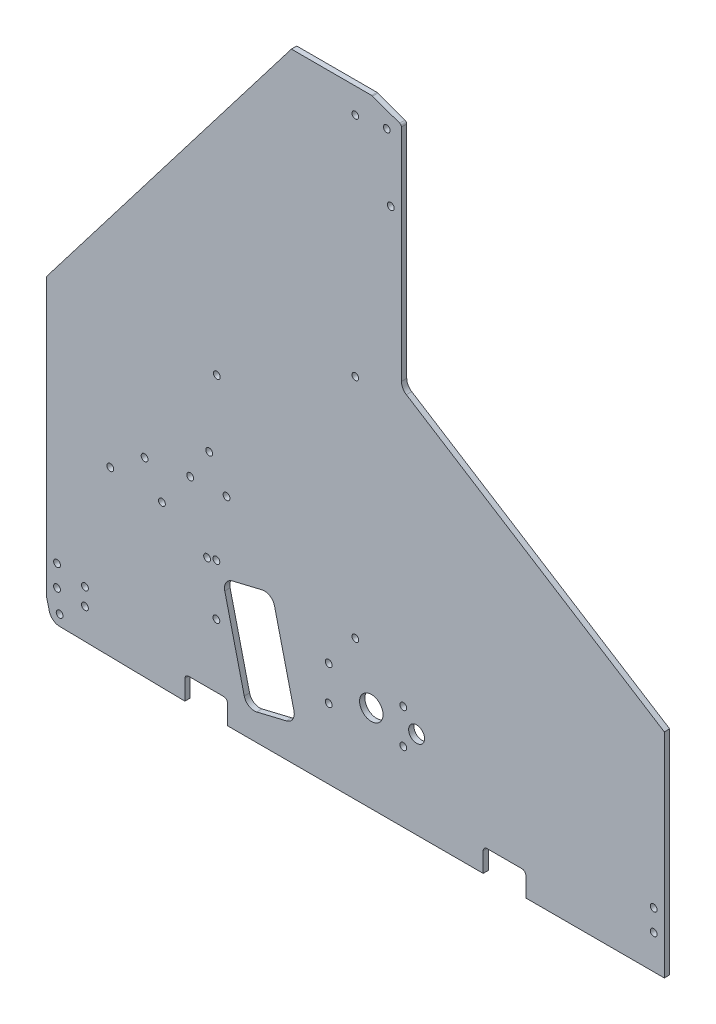
SolidWorks part; units mm, degrees
ref_plane "Front Plane" through (0, 0, 0) normal (0, 0, 1) x (1, 0, 0)
ref_plane "Top Plane" through (0, 0, 0) normal (0, 1, 0) x (1, 0, 0)
ref_plane "Right Plane" through (0, 0, 0) normal (1, 0, 0) x (0, 0, -1)
sketch "Sketch1" plane through (0, 0, 0) normal (0, 0, 1) x (1, 0, 0)
  line L0 (82.55, -20.32) -> (82.55, -6.35)
  line L2 (0, 0) -> (0, 157.48)
  line L4 (368.3, -20.32) -> (368.3, 106.68)
  line L5 (82.55, -6.35) -> (107.95, -6.35)
  line L6 (107.95, -6.35) -> (107.95, -20.32)
  line L7 (107.95, -20.32) -> (260.35, -20.32)
  line L8 (260.35, -20.32) -> (260.35, -6.35)
  line L9 (260.35, -6.35) -> (285.75, -6.35)
  line L10 (285.75, -6.35) -> (285.75, -20.32)
  line L11 (285.75, -20.32) -> (368.3, -20.32)
  line L12 (361.95, 12.7) -> (368.3, 12.7) construction
  line L13 (0, 0) -> (6.35, 0) construction
  line L14 (0.1896, -7.8901) -> (1.7771, -14.2401)
  line L15 (7.8295, -19.0491) -> (82.55, -20.32)
  line L16 (0, 0) -> (0, -6.35)
  line L17 (85.725, 97.155) -> (82.9754, 95.5675) construction
  line L18 (97.0634, 115.6163) -> (58.5686, 93.3913) construction
  line L19 (97.0634, 115.6163) -> (107.3822, 97.7437) construction
  line L20 (58.5686, 93.3913) -> (68.8873, 75.5187) construction
  line L21 (107.3822, 97.7437) -> (68.8873, 75.5187) construction
  line L22 (97.0634, 115.6163) -> (68.8873, 75.5187) construction
  line L23 (58.5686, 93.3913) -> (107.3822, 97.7437) construction
  line L24 (7.9375, -12.7) -> (95.7973, 60.4105) construction
  line L25 (184.15, 62.98) -> (184.15, 197.98) construction
  line L26 (184.15, 197.98) -> (184.15, 332.98) construction
  line L27 (355.6, 335.28) -> (330.2, 335.28) construction
  line L28 (330.2, 335.28) -> (330.2, 220.98) construction
  line L29 (330.2, 220.98) -> (355.6, 220.98) construction
  line L30 (355.6, 220.98) -> (355.6, 335.28) construction
  line L31 (184.15, 347.98) -> (184.15, 269.4703) construction
  line L32 (12.7, 335.28) -> (38.1, 335.28) construction
  line L33 (38.1, 335.28) -> (38.1, 220.98) construction
  line L34 (12.7, 220.98) -> (12.7, 335.28) construction
  line L35 (38.1, 220.98) -> (12.7, 220.98) construction
  line L36 (194.15, 347.98) -> (211.6138, 341.63)
  line L37 (184.15, 347.98) -> (146.05, 347.98)
  line L38 (184.15, 347.98) -> (194.15, 347.98)
  line L39 (348.5362, 347.98) -> (413.4623, 347.98)
  line L40 (348.5362, 347.98) -> (211.6138, 347.98) construction
  line L42 (146.05, 347.98) -> (0, 157.48)
  line L44 (211.6138, 341.63) -> (211.6138, 205.74)
  line L45 (211.6138, 205.74) -> (368.3, 106.68)
  line L46 (194.15, 347.98) -> (-141.0713, 347.98) construction
  circle A0 centre (6.35, 0) radius 2.032
  circle A1 centre (6.35, 12.7) radius 2.032
  circle A2 centre (361.95, 0) radius 2.032
  circle A3 centre (361.95, 12.7) radius 2.032
  arc A5 (1.7771, -14.2401) -> (7.8295, -19.0491) centre (7.9375, -12.7) ccw
  circle A6 centre (7.9375, -12.7) radius 2.032
  arc A7 (0, -6.35) -> (0.1896, -7.8901) centre (6.35, -6.35) ccw
  circle A8 centre (38.1, 78.105) radius 2.032
  circle A9 centre (85.725, 97.155) radius 2.032
  circle A10 centre (58.5686, 93.3913) radius 2.032
  circle A11 centre (68.8873, 75.5187) radius 2.032
  circle A12 centre (107.3822, 97.7437) radius 2.032
  circle A13 centre (97.0634, 115.6163) radius 2.032
  circle A14 centre (95.7973, 60.4105) radius 2.032
  circle A15 centre (184.15, 62.98) radius 2
  circle A16 centre (184.15, 197.98) radius 2
  circle A17 centre (184.15, 332.98) radius 2
  circle A18 centre (63.5, 316.23) radius 2.032
  circle A19 centre (101.6, 157.48) radius 2.032
  circle A20 centre (355.6, 335.28) radius 2.032
  circle A21 centre (330.2, 335.28) radius 2.032
  circle A22 centre (355.6, 220.98) radius 2.032
  circle A23 centre (330.2, 220.98) radius 2.032
  circle A24 centre (12.7, 335.28) radius 2.032
  circle A25 centre (38.1, 335.28) radius 2.032
  circle A26 centre (12.7, 220.98) radius 2.032
  circle A27 centre (38.1, 220.98) radius 2.032
  circle A28 centre (202.8819, 335.28) radius 2
  circle A29 centre (205.2638, 296.418) radius 2.032
  point P82 (184.15, 347.98)
  point P83 (202.8819, 344.805)
  dimension "D6" = 4.064
  dimension "D10" = 6.35
  dimension "D11" = 4.064
  dimension "D17" = 38.1
  dimension "D27" = 4
  dimension "D31" = 4.064
  dimension "D32" = 38.1
  dimension "D36" = 4.064
  dimension "D47" = 45.212
  dimension "D48" = 4.064
  dimension "D2" = 127
  dimension "D3" = 13.97
  dimension "D4" = 25.4
  dimension "D5" = 152.4
  dimension "D7" = 12.7
  dimension "D8" = 6.35
  dimension "D9" = 20.32
  dimension "D12" = 12.7
  dimension "D13" = 1.5875
  dimension "D14" = 82.55
  dimension "D15" = 368.3
  dimension "D16" = 6.35
  dimension "D18" = 98.425
  dimension "D19" = 47.625
  dimension "D20" = 19.05
  dimension "D21" = 3.175
  dimension "D22" = 60
  dimension "D23" = 20.6375
  dimension "D24" = 44.45
  dimension "D25" = 38.1
  dimension "D26" = 114.3
  dimension "D28" = 135
  dimension "D29" = 12.7
  dimension "D30" = 15
  dimension "D33" = 63.5
  dimension "D34" = 27.4638
  dimension "D35" = 101.6
  dimension "D37" = 114.3
  dimension "D38" = 25.4
  dimension "D39" = 12.7
  dimension "D40" = 157.48
  dimension "D41" = 142.24
  dimension "D42" = 368.3
  dimension "D43" = 10
  dimension "D44" = 6.35
  dimension "D45" = 31.75
  dimension "D46" = 6.35
  dimension "D49" = 6.35
extrude "Boss-Extrude1" add sketch "Sketch1" along normal blind 3.175 contours L16 A7 L14 A5 L15 L2 A0 A1 A6 region at (167.8922, 118.3155, 0)
fillet "Fillet1" radius 2.286 4 edges at (285.75, -6.35, 1.5875) (107.95, -6.35, 1.5875) (260.35, -6.35, 1.5875) (82.55, -6.35, 1.5875)
fillet "Fillet2" radius 6.35 1 edges at (211.6138, 205.74, 1.5875)
sketch "Sketch2" plane through (0, 0, 0) normal (0, 0, -1) x (-1, 0, 0)
  circle A0 centre (-101.3398, 61.8475) radius 2.032 construction
  circle A1 centre (-101.3398, 31.3675) radius 2.032 construction
  circle A2 centre (-23.012, 8.964) radius 2.032 construction
  circle A3 centre (-23.012, -1.196) radius 2.032 construction
  circle A4 centre (-101.3398, 61.8475) radius 2.032
  circle A5 centre (-101.3398, 31.3675) radius 2.032
  circle A6 centre (-23.012, 8.964) radius 2.032
  circle A7 centre (-23.012, -1.196) radius 2.032
extrude "Cut-Extrude1" cut sketch "Sketch2" against normal through all
fillet "Fillet3" radius 1.5875 2 edges at (211.6138, 341.63, 1.5875) (194.15, 347.98, 1.5875)
sketch "Sketch3" plane through (0, 0, 3.175) normal (0, 0, 1) x (1, 0, 0)
  line L0 (133.7394, 54.026) -> (133.5085, 54.9896) construction
  line L1 (129.1684, 57.6512) -> (111.4698, 53.4086) construction
  line L2 (115.3002, 49.1851) -> (127.6692, 52.1501) construction
  line L3 (108.8082, 49.0686) -> (109.0392, 48.1051) construction
  line L4 (131.9876, 48.4644) -> (140.8034, 11.688) construction
  line L5 (144.8863, 7.5251) -> (133.7394, 54.026) construction
  line L6 (109.0392, 48.1051) -> (120.1861, 1.6041) construction
  line L7 (121.9379, 7.1657) -> (113.1221, 43.9421) construction
  line L8 (120.1861, 1.6041) -> (120.4171, 0.6406) construction
  line L9 (145.1173, 6.5615) -> (144.8863, 7.5251) construction
  line L10 (138.6253, 6.445) -> (126.2564, 3.48) construction
  line L11 (124.7571, -2.0211) -> (142.4557, 2.2215) construction
  line L12 (133.7394, 54.026) -> (133.5085, 54.9896)
  line L13 (129.1684, 57.6512) -> (111.4698, 53.4086)
  line L14 (115.3002, 49.1851) -> (127.6692, 52.1501)
  line L15 (108.8082, 49.0686) -> (109.0392, 48.1051)
  line L16 (131.9876, 48.4644) -> (140.8034, 11.688)
  line L17 (144.8863, 7.5251) -> (133.7394, 54.026)
  line L18 (109.0392, 48.1051) -> (120.1861, 1.6041)
  line L19 (121.9379, 7.1657) -> (113.1221, 43.9421)
  line L20 (120.1861, 1.6041) -> (120.4171, 0.6406)
  line L21 (145.1173, 6.5615) -> (144.8863, 7.5251)
  line L22 (138.6253, 6.445) -> (126.2564, 3.48)
  line L23 (124.7571, -2.0211) -> (142.4557, 2.2215)
  line L24 (128.5763, 60.1212) -> (110.8777, 55.8786)
  line L25 (106.3382, 48.4765) -> (106.5692, 47.513)
  line L26 (106.5692, 47.513) -> (117.7161, 1.012)
  line L27 (117.7161, 1.012) -> (117.947, 0.0485)
  line L28 (125.3492, -4.4911) -> (143.0478, -0.2485)
  line L29 (147.5873, 7.1536) -> (147.3564, 8.1172)
  line L30 (147.3564, 8.1172) -> (136.2095, 54.6181)
  line L31 (136.2095, 54.6181) -> (135.9785, 55.5817)
  arc A0 (133.5085, 54.9896) -> (129.4178, 57.7017) centre (130.0076, 54.1504) ccw construction
  arc A1 (111.4698, 53.4086) -> (111.2247, 53.3406) centre (112.309, 49.9078) ccw construction
  arc A2 (129.4178, 57.7017) -> (129.1684, 57.6512) centre (130.0076, 54.1504) ccw construction
  arc A3 (111.2247, 53.3406) -> (108.8082, 49.0686) centre (112.309, 49.9078) ccw construction
  arc A4 (120.4171, 0.6406) -> (124.5077, -2.0716) centre (123.9179, 1.4797) ccw construction
  arc A5 (142.7009, 2.2895) -> (145.1173, 6.5615) centre (141.6165, 5.7223) ccw construction
  arc A6 (142.4557, 2.2215) -> (142.7009, 2.2895) centre (141.6165, 5.7223) ccw construction
  arc A7 (124.5077, -2.0716) -> (124.7571, -2.0211) centre (123.9179, 1.4797) ccw construction
  arc A8 (133.5085, 54.9896) -> (129.4178, 57.7017) centre (130.0076, 54.1504) ccw
  arc A9 (111.4698, 53.4086) -> (111.2247, 53.3406) centre (112.309, 49.9078) ccw
  arc A10 (129.4178, 57.7017) -> (129.1684, 57.6512) centre (130.0076, 54.1504) ccw
  arc A11 (111.2247, 53.3406) -> (108.8082, 49.0686) centre (112.309, 49.9078) ccw
  arc A12 (120.4171, 0.6406) -> (124.5077, -2.0716) centre (123.9179, 1.4797) ccw
  arc A13 (142.7009, 2.2895) -> (145.1173, 6.5615) centre (141.6165, 5.7223) ccw
  arc A14 (142.4557, 2.2215) -> (142.7009, 2.2895) centre (141.6165, 5.7223) ccw
  arc A15 (124.5077, -2.0716) -> (124.7571, -2.0211) centre (123.9179, 1.4797) ccw
  arc A16 (110.8777, 55.8786) -> (110.4596, 55.7626) centre (112.309, 49.9078) ccw
  arc A17 (110.4596, 55.7626) -> (106.3382, 48.4765) centre (112.309, 49.9078) ccw
  arc A18 (117.947, 0.0485) -> (124.9239, -4.5773) centre (123.9179, 1.4797) ccw
  arc A19 (124.9239, -4.5773) -> (125.3492, -4.4911) centre (123.9179, 1.4797) ccw
  arc A20 (143.0478, -0.2485) -> (143.4659, -0.1325) centre (141.6165, 5.7223) ccw
  arc A21 (143.4659, -0.1325) -> (147.5873, 7.1536) centre (141.6165, 5.7223) ccw
  arc A22 (135.9785, 55.5817) -> (129.0017, 60.2074) centre (130.0076, 54.1504) ccw
  arc A23 (129.0017, 60.2074) -> (128.5763, 60.1212) centre (130.0076, 54.1504) ccw
  ellipse E0 centre (125.3844, 39.6102) end of major axis (129.3246, 52.1192) minor radius 6 (131.9876, 48.4644) -> (127.6692, 52.1501) ccw construction
  ellipse E1 centre (123.0219, 39.0439) end of major axis (113.8388, 48.407) minor radius 6 (115.3002, 49.1851) -> (113.1221, 43.9421) ccw construction
  ellipse E2 centre (128.5411, 16.0199) end of major axis (132.4812, 28.5289) minor radius 6 (121.9379, 7.1657) -> (126.2564, 3.48) ccw construction
  ellipse E3 centre (130.9036, 16.5863) end of major axis (140.0868, 7.2231) minor radius 6 (138.6253, 6.445) -> (140.8034, 11.688) ccw construction
  ellipse E4 centre (125.3844, 39.6102) end of major axis (121.4443, 27.1012) minor radius 6 (131.9876, 48.4644) -> (127.6692, 52.1501) ccw
  ellipse E5 centre (123.0219, 39.0439) end of major axis (113.8388, 48.407) minor radius 6 (115.3002, 49.1851) -> (113.1221, 43.9421) ccw
  ellipse E6 centre (128.5411, 16.0199) end of major axis (132.4812, 28.5289) minor radius 6 (121.9379, 7.1657) -> (126.2564, 3.48) ccw
  ellipse E7 centre (130.9036, 16.5863) end of major axis (140.0868, 7.2231) minor radius 6 (138.6253, 6.445) -> (140.8034, 11.688) ccw
  dimension "D1" = 2.54
extrude "Cut-Extrude2" cut sketch "Sketch3" against normal through all contours A22 A23 L24 A16 A17 L25 L26 L27 A18 A19 L28 A20 A21 L29 L30 L31 A15 A12 L20 L18 L15 A11 A9 L13 A10 A8 L12 L17 L21 A13 A14 L23 | A12 A15 L23 A14 A13 L21 L17 L12 A8 A10 L13 A9 A11 L15 L18 L20 E7 L22 E6 L19 E5 L14 E4 L16 | L22 E7 L16 E4 L14 E5 L19 E6 region at (138.631, 30.6121, 3.175) region at (126.9628, 27.8151, 3.175) region at (128.9414, 59.4122, 3.175)
sketch "Sketch4" plane through (0, 0, 3.175) normal (0, 0, 1) x (1, 0, 0)
  line L0 (107.3822, 97.7437) -> (68.8873, 75.5187) construction
  line L1 (168.275, 21.4312) -> (212.725, 21.4312) construction
  line L2 (168.275, 21.4312) -> (168.275, 42.0687) construction
  line L3 (168.275, 42.0687) -> (212.725, 42.0687) construction
  line L4 (212.725, 21.4312) -> (212.725, 42.0687) construction
  line L5 (168.275, 21.4312) -> (212.725, 42.0687) construction
  line L6 (168.275, 42.0687) -> (212.725, 21.4312) construction
  line L7 (97.0634, 115.6163) -> (107.3822, 97.7437) construction
  line L8 (107.95, -20.32) -> (260.35, -20.32) construction
  line L10 (190.5, 31.75) -> (193.675, 31.75) construction
  line L11 (6.35, 12.7) -> (361.95, 12.7) construction
  line L12 (107.95, -6.35) -> (107.95, -20.32) construction
  line L13 (193.675, 31.75) -> (220.6625, 31.75) construction
  line L15 (194.15, 47.98) -> (174.15, 47.98) construction
  line L16 (194.15, 47.98) -> (194.15, 347.98) construction
  line L17 (194.15, 347.98) -> (174.15, 347.98) construction
  line L18 (174.15, 47.98) -> (174.15, 347.98) construction
  line L19 (194.15, 47.98) -> (174.15, 347.98) construction
  line L20 (194.15, 347.98) -> (174.15, 47.98) construction
  circle A0 centre (168.275, 42.0687) radius 2.032
  circle A1 centre (212.725, 42.0687) radius 2.032
  circle A2 centre (212.725, 21.4312) radius 2.032
  circle A3 centre (168.275, 21.4312) radius 2.032
  circle A4 centre (193.675, 31.75) radius 6.985
  circle A5 centre (220.6625, 31.75) radius 4.7625
  circle A7 centre (220.6625, 31.75) radius 14.2875 construction
  circle A8 centre (193.675, 31.75) radius 12.7 construction
  point P0 (190.5, 31.75)
  point P26 (184.15, 197.98)
  dimension "D1" = 4.064
  dimension "D4" = 13.97
  dimension "D7" = 9.525
  dimension "D10" = 25.4
  dimension "D11" = 28.575
  dimension "D2" = 52.07
  dimension "D3" = 3.175
  dimension "D5" = 82.55
  dimension "D6" = 26.9875
  dimension "D8" = 20
  dimension "D9" = 300
extrude "Cut-Extrude3" cut sketch "Sketch4" against normal through all
